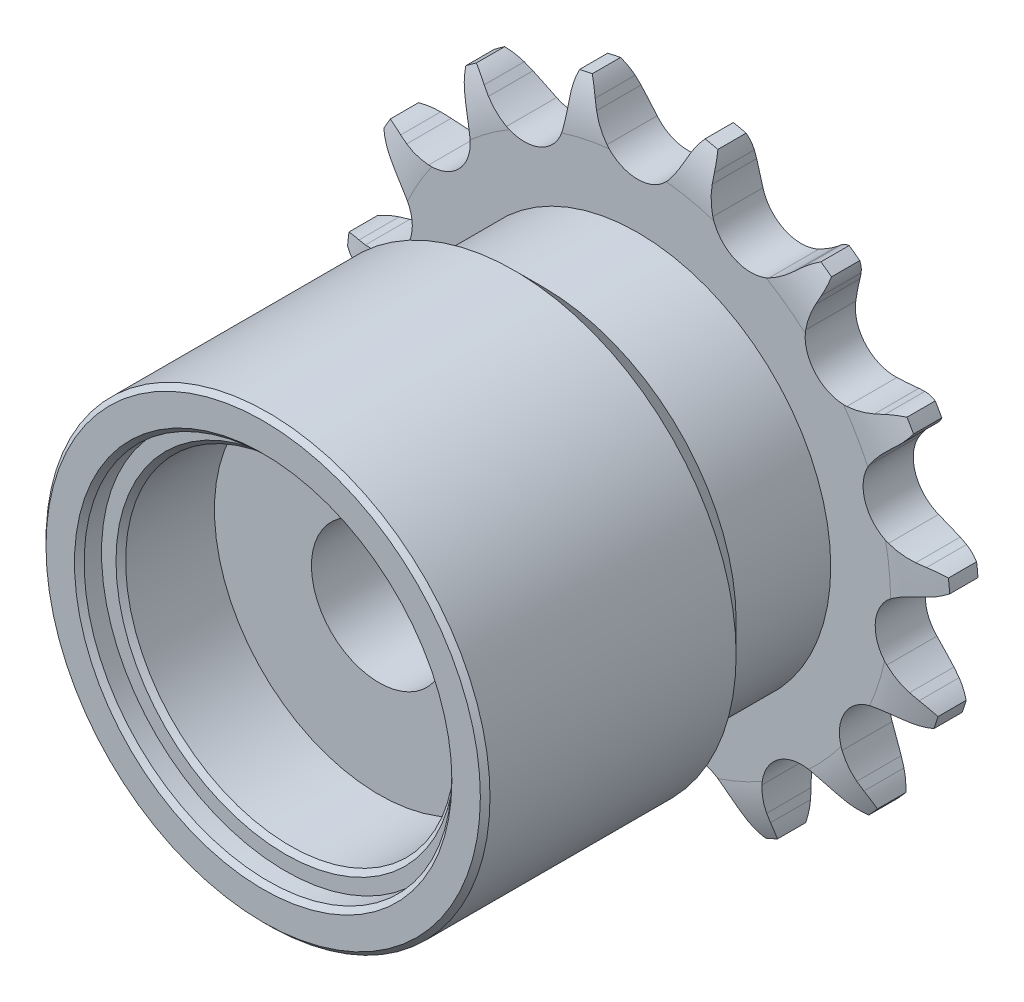
SolidWorks part; units mm, degrees
ref_plane "Front Plane" through (0, 0, 0) normal (0, 0, 1) x (1, 0, 0)
ref_plane "Top Plane" through (0, 0, 0) normal (0, 1, 0) x (1, 0, 0)
ref_plane "Right Plane" through (0, 0, 0) normal (1, 0, 0) x (0, 0, -1)
sketch "Sketch0" plane through (0, 0, 0) normal (0, 0, 1) x (1, 0, 0)
  line L0 (3, -14.1139) -> (0, 0) construction
  line L1 (0, 0) -> (8.4813, -11.6735) construction
  line L2 (0, 0) -> (-3, -14.1139) construction
  line L3 (3, -14.1139) -> (8.4813, -11.6735) construction
  line L4 (3, -14.1139) -> (-3, -14.1139) construction
  line L5 (5.4587, -13.8191) -> (5.1921, -13.4619)
  line L6 (3, -14.1139) -> (0, -14.7516) construction
  line L7 (0.6339, -14.8447) -> (0.7322, -14.4099)
  line L8 (0, -14.1139) -> (0, -15.9139) construction
  line L9 (4.2889, -12.5222) -> (0.9862, -16.6008) construction
  line L10 (0, 0) -> (0, -14.1139) construction
  line L11 (5.1921, -13.4619) -> (0.9862, -16.6008) construction
  line L12 (0, -15.9139) -> (0, -16.1712) construction
  line L13 (8.1159, -11.8362) -> (5.4587, -13.8191) construction
  circle A0 centre (0, 0) radius 15.9139 construction
  circle A1 centre (0, 0) radius 14.4292 construction
  arc A2 (-3.2007, -17.3745) -> (9.9908, -14.5706) centre (0, 0) ccw
  circle A3 centre (0, 0) radius 16.1712 construction
  circle A4 centre (3, -14.1139) radius 2 construction
  arc A7 (4.2889, -12.5222) -> (1.1751, -13.1841) centre (3, -14.1139) ccw
  circle A8 centre (3, -14.1139) radius 2.0481 construction
  arc A9 (5.4587, -13.8191) -> (9.9908, -14.5706) centre (8.1159, -11.8362) ccw
  arc A10 (5.1921, -13.4619) -> (4.2889, -12.5222) centre (0.9862, -16.6008) ccw
  arc A11 (0.6339, -14.8447) -> (-3.2007, -17.3745) centre (-2.6, -14.1139) cw
  arc A12 (0.7322, -14.4099) -> (1.1751, -13.1841) centre (5.8512, -15.5667) cw
  dimension "D1" = 2.0481
  dimension "R" = 2.0481
sketch "Sketch1" plane through (0, 0, 0) normal (1, 0, 0) x (0, 0, -1)
  line L0 (1.3, 0) -> (-1.3, 0)
  line L1 (-1.3, 0) -> (-1.3, 13.1014)
  line L2 (-1.3, 14.4292) -> (0, 14.4292) construction
  line L3 (-0.6, 15.9139) -> (0.6, 15.9139)
  line L5 (1.3, 13.1014) -> (1.3, 0)
  line L7 (0, 15.9139) -> (0, 0) construction
  line L8 (-1.3, 13.1014) -> (1.3, 13.1014) construction
  line L9 (0, 15.9139) -> (0, -15.9139) construction
  line L10 (-1.3, 13.1014) -> (-1.3, 15.9139) construction
  line L11 (-1.3, 15.9139) -> (-0.6, 15.9139) construction
  line L12 (0.6, 15.9139) -> (1.3, 15.9139) construction
  line L13 (1.3, 15.9139) -> (1.3, 13.1014) construction
  line L14 (0, 0) -> (-6.4008, 0) construction
  line L15 (-1.3, 14.4292) -> (-1.3, 10.3292) construction
  line L22 (1.3, 0) -> (-8.7, 0) construction
  line L24 (-1.3, 0) -> (-1.3, 10.3292) construction
  arc A0 (-0.6, 15.9139) -> (-1.3, 13.1014) centre (4.7, 13.1014) ccw
  arc A1 (0.6, 15.9139) -> (1.3, 13.1014) centre (-4.7, 13.1014) cw
  dimension "R" = 6
revolve "Revolve1" add sketch "Sketch1" angle 360 mid plane about L0
extrude "Cut-Extrude1" cut sketch "Sketch0" against normal through all and the other way through all
pattern_circular "CirPattern1" count 15 over 360 about axis through (0, 0, -1.3) along (0, 0, -1) of "Cut-Extrude1"
sketch "Sketch2" plane through (0, 0, 0) normal (0, 0, 1) x (1, 0, 0)
  circle A0 centre (0, 0) radius 3 construction
  circle A1 centre (0, 0) radius 10
  circle A2 centre (0, 0) radius 15.65 construction
  dimension "Bore" = 6
  dimension "Hub Dia." = 20
  dimension "OD" = 31.3
extrude "Boss-Extrude1" add sketch "Sketch2" along normal up to vertex (8.7 mm away) from surface up to point (0, 0, 8.7) starting at face at (0, 0, 1.3)
sketch "Sketch3" plane through (0, 0, 0) normal (0, 0, 1) x (1, 0, 0)
  circle A0 centre (0, 0) radius 3 construction
  circle A1 centre (0, 0) radius 3
extrude "Cut-Extrude2" cut sketch "Sketch3" along normal through all and the other way through all
sketch "Sketch4" plane through (0, 0, 0) normal (1, 0, 0) x (0, 0, -1)
  line L0 (-8.7, 10) -> (-8.7, 9.5)
  line L1 (-1.3, 15.9139) -> (-3.25, 15.9139)
  line L2 (-1.3, 15.9139) -> (-1.3, 10.3292)
  line L3 (-1.3, 10.3292) -> (-3.25, 10.3292)
  line L4 (-3.25, 15.9139) -> (-3.25, 10.3292)
  line L9 (-8.7, 9.5) -> (-8.2, 10)
  line L10 (-8.2, 10) -> (-8.7, 10)
  dimension "C" = 0.5
  dimension "D3" = 1.95
revolve "Cut-Revolve1" cut sketch "Sketch4" angle 360 mid plane about L22
sketch "Sketch5" plane through (0, 0, 0) normal (0, 0, 1) x (1, 0, 0)
  circle A0 centre (0, 0) radius 15.65 construction
  circle A1 centre (0, 0) radius 15.65
extrude "Cut-Extrude3" cut sketch "Sketch5" against normal through all and the other way through all flip side to cut
sketch "Sketch6" plane through (0, 0, 0) normal (0, 0, 1) x (1, 0, 0)
  circle A0 centre (0, 0) radius 3.5
  dimension "D1" = 7
extrude "Cut-Extrude4" cut sketch "Sketch6" along normal through all both and the other way through all
ref_plane "Plane1" through (0, 0, 8.2) normal (0, 0, 1) x (1, 0, 0)
sketch "Sketch7" plane through (0, 0, 8.2) normal (0, 0, 1) x (1, 0, 0)
  circle A0 centre (0, 0) radius 11.5
  circle A1 centre (0, 0) radius 3.5
  dimension "D1" = 23
  dimension "D2" = 7
extrude "Boss-Extrude2" add sketch "Sketch7" along normal blind 12.5
sketch "Sketch8" plane through (0, 0, 20.7) normal (0, 0, 1) x (1, 0, 0)
  circle A0 centre (0, 0) radius 8.525
  dimension "D1" = 17.05
extrude "Cut-Extrude5" cut sketch "Sketch8" against normal blind 6
sketch "Sketch9" plane through (0, 0, 20.7) normal (0, 0, 1) x (1, 0, 0)
  circle A0 centre (0, 0) radius 9.525
  dimension "D1" = 19.05
extrude "Cut-Extrude6" cut sketch "Sketch9" against normal blind 1.15
chamfer "Chamfer1" distance 2 angle 45 1 edges at (10, 0, 8.2)
chamfer "Chamfer2" distance 0.25 angle 45 3 edges at (11.5, 0, 20.7) (9.525, 0, 20.7) (8.525, 0, 19.55)
equation "\"360/N@Sketch0\" = 360/\"Teeth@CirPattern1\""
equation "\"Ds@Sketch0\" = 1.005 * \"Dr@Sketch0\" + ( 0.003 * 25.4 ) "
equation "\"R@Sketch0\" = 1/2 * \"Ds@Sketch0\""
equation "\"A@Sketch0\" = 35 +  ( 60 / \"Teeth@CirPattern1\" ) "
equation "\"B@Sketch0\" = 18 -  ( 56 / \"Teeth@CirPattern1\" )"
equation "\"ac@Sketch0\" = 0.8 * \"Dr@Sketch0\""
equation "\"ab@Sketch0\" = 1.4 * \"Dr@Sketch0\""
equation "\"J@Sketch0\" = 0.3 * \"Pitch@Sketch0\""
equation "\"D3@Sketch4\" = \"t@Sketch1\" * 3 / 4"
